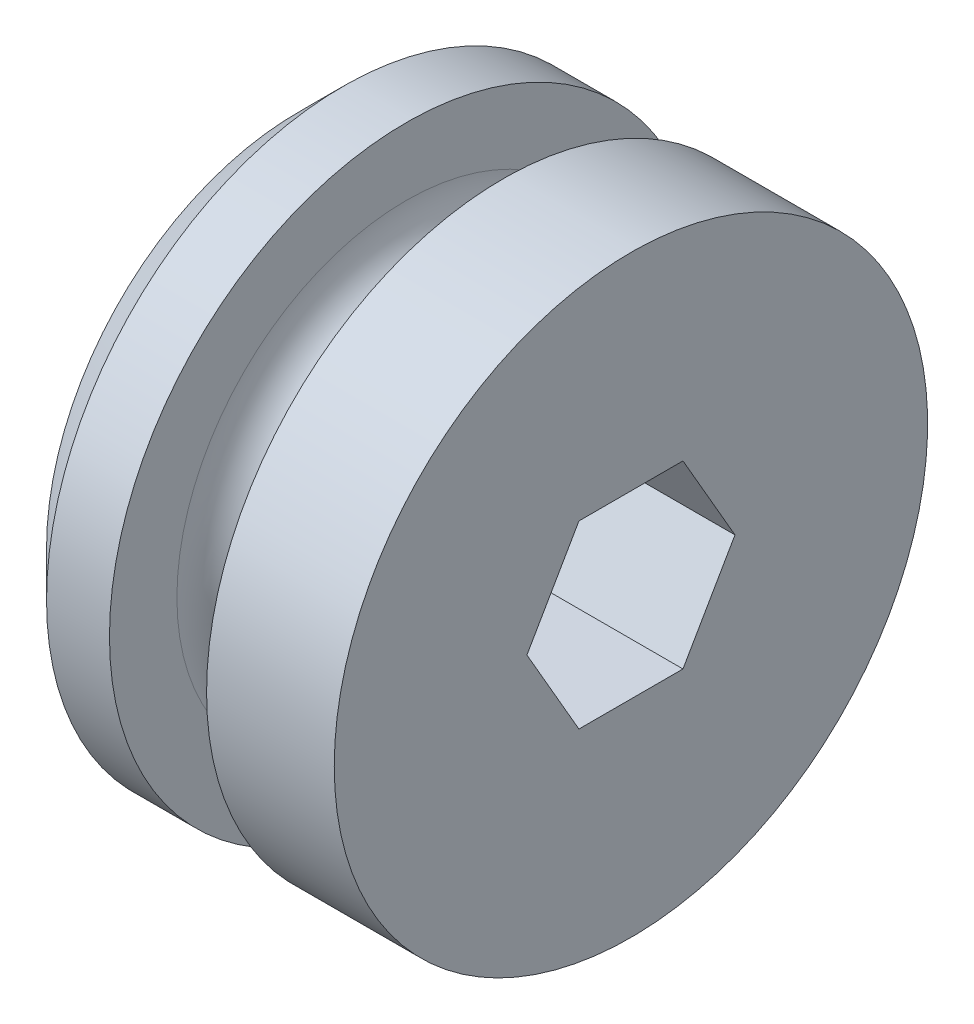
SolidWorks part; units mm, degrees
material "PET"
ref_plane "Front Plane" through (0, 0, 0) normal (0, 0, 1) x (1, 0, 0)
ref_plane "Top Plane" through (0, 0, 0) normal (0, 1, 0) x (1, 0, 0)
ref_plane "Right Plane" through (0, 0, 0) normal (1, 0, 0) x (0, 0, -1)
sketch "Sketch1" plane through (0, 0, 0) normal (0, 0, 1) x (1, 0, 0)
  line L0 (23.495, 0) -> (0, 0)
  line L1 (0, 0) -> (23.495, 0) construction
  line L2 (0, 0) -> (0, 20.955)
  line L3 (0, 20.955) -> (7.62, 20.955)
  line L4 (7.62, 16.1925) -> (7.62, 20.955)
  line L6 (14.478, 16.1925) -> (14.478, 20.955)
  line L7 (14.478, 20.955) -> (23.495, 20.955)
  line L8 (23.495, 0) -> (23.495, 20.955)
  line L9 (11.049, 12.7635) -> (11.049, 0) construction
  arc A0 (7.62, 16.1925) -> (14.478, 16.1925) centre (11.049, 16.1925) ccw
  dimension "D1" = 3.429
  dimension "D2" = 23.495
  dimension "D3" = 20.955
  dimension "D4" = 4.7625
  dimension "D5" = 7.62
  dimension "D7" = 12.7635
revolve "Revolve1" add sketch "Sketch1" angle 360 about L1 region at (11.8284, 9.6998, 0)
chamfer "Chamfer1" distance 3.175 angle 45 1 edges at (0, 0, 20.955)
sketch "Sketch2" plane through (0, 0, 0) normal (-1, 0, 0) x (0, 0, 1)
  line L1 (3.6735, -6.3627) -> (7.347, 0)
  line L2 (7.347, 0) -> (3.6735, 6.3627)
  line L3 (3.6735, 6.3627) -> (-3.6735, 6.3627)
  line L4 (-3.6735, 6.3627) -> (-7.347, 0)
  line L5 (-7.347, 0) -> (-3.6735, -6.3627)
  line L6 (-3.6735, -6.3627) -> (3.6735, -6.3627)
  circle A0 centre (0, 0) radius 6.3627 construction
  dimension "D1" = 12.7254
extrude "Cut-Extrude1" cut sketch "Sketch2" against normal through all
